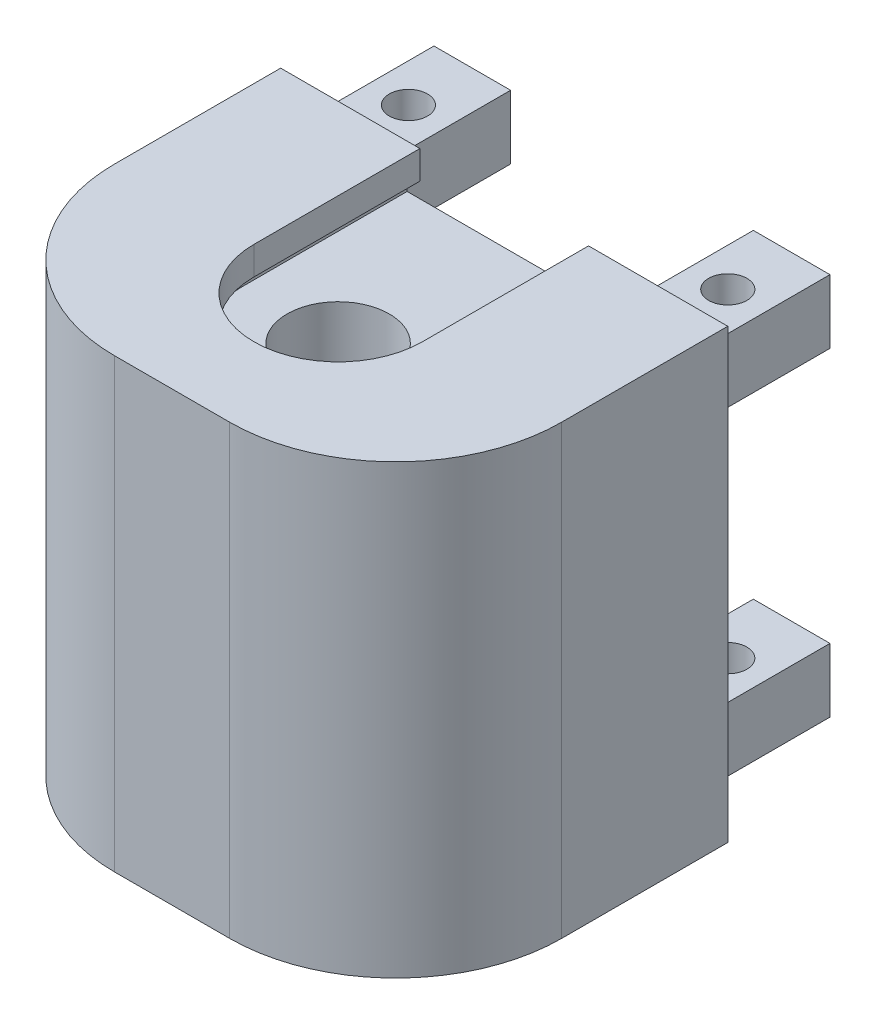
SolidWorks part; units mm, degrees
ref_plane "Front Plane" through (0, 0, 0) normal (0, 0, 1) x (1, 0, 0)
ref_plane "Top Plane" through (0, 0, 0) normal (0, 1, 0) x (1, 0, 0)
ref_plane "Right Plane" through (0, 0, 0) normal (1, 0, 0) x (0, 0, -1)
sketch "Sketch1" plane through (0, 0, 0) normal (0, 1, 0) x (1, 0, 0)
  line L0 (0, 0) -> (6, 0)
  line L1 (6, 0) -> (6, -10)
  line L2 (6, -10) -> (25, -10)
  line L3 (25, -10) -> (25, 0)
  line L4 (25, 0) -> (31, 0)
  line L5 (31, 0) -> (31, -10)
  line L7 (0, -10) -> (0, 0)
  line L8 (0, -10) -> (-2, -10)
  line L11 (33, -36) -> (33, -10)
  line L12 (33, -10) -> (31, -10)
  line L13 (3, 0) -> (3, -5) construction
  line L14 (15.5, -10) -> (15.5, 0) construction
  line L15 (33, -36) -> (-2, -36)
  line L16 (-2, -36) -> (-2, -10)
  circle A0 centre (3, -5) radius 1.5
  circle A1 centre (28, -5) radius 1.5
  dimension "D9" = 3
  dimension "D1" = 36
  dimension "D2" = 35
  dimension "D3" = 10
  dimension "D4" = 6
  dimension "D5" = 2
  dimension "D6" = 6
  dimension "D7" = 2
  dimension "D8" = 5
sketch "Sketch10" plane through (0, 0, 0) normal (0, 1, 0) x (1, 0, 0)
  line L0 (-2, -36) -> (33, -36)
  line L1 (33, -36) -> (33, -10)
  line L2 (33, -10) -> (-2, -10)
  line L3 (-2, -36) -> (-2, -10)
extrude "Boss-Extrude4" add sketch "Sketch10" along normal blind 2.5
extrude "Boss-Extrude5" add sketch "Sketch1" against normal blind 5
sketch "Sketch11" plane through (0, -5, 0) normal (0, -1, 0) x (1, 0, 0)
  line L0 (-2, 36) -> (-2, 10)
  line L1 (-2, 10) -> (33, 10)
  line L2 (33, 10) -> (33, 36)
  line L3 (33, 36) -> (-2, 36)
extrude "Boss-Extrude6" add sketch "Sketch11" along normal blind 2.5
ref_plane "Plane1" through (0, -2.5, 0) normal (0, 1, 0) x (1, 0, 0)
sketch "Sketch3" plane through (0, 0, 10) normal (0, 0, -1) x (-1, 0, 0)
  line L0 (-22.1, 2.5) -> (-22.1, 0.2875)
  line L2 (-22.1, 0.2875) -> (-23.1, 0.2875)
  line L3 (-23.1, 0.2875) -> (-23.1, -0.9125)
  line L4 (-23.1, -0.9125) -> (-15.5, -0.9125)
  line L5 (-15.5, -0.9125) -> (-7.9, -0.9125)
  line L6 (-7.9, -0.9125) -> (-7.9, 0.2875)
  line L7 (-7.9, 0.2875) -> (-8.9, 0.2875)
  line L8 (-8.9, 0.2875) -> (-8.9, 2.5)
  line L9 (-8.9, 2.5) -> (-22.1, 2.5)
  line L10 (-25, -2.5) -> (-6, -2.5) construction
  line L13 (-15.5, -2.5) -> (-15.5, -0.9125) construction
  line L14 (-33, 2.5) -> (2, 2.5) construction
  line L15 (-6, -5) -> (-6, 0) construction
  line L16 (-25, -5) -> (-25, 0) construction
  dimension "D1" = 1.2
  dimension "D2" = 3.4125
  dimension "D3" = 13.2
  dimension "D4" = 15.2
extrude "Cut-Extrude1" cut sketch "Sketch3" against normal blind 13 and the other way through all
sketch "Sketch4" plane through (0, -0.9125, 0) normal (0, 1, 0) x (1, 0, 0)
  line L1 (23.1, -23) -> (7.9, -23) construction
  circle A0 centre (15.5, -23) radius 7.6
  dimension "D1" = 15.2
extrude "Cut-Extrude2" cut sketch "Sketch4" along normal up to surface (1.2 mm away) up to face at (8.4, 0.2875, 16.5)
sketch "Sketch5" plane through (0, -0.9125, 0) normal (0, 1, 0) x (1, 0, 0)
  line L1 (8.9, -23) -> (22.1, -23) construction
  circle A0 centre (15.5, -23) radius 6.6
  dimension "D1" = 13.2
extrude "Cut-Extrude3" cut sketch "Sketch5" along normal through all
sketch "Sketch12" plane through (0, -7.5, 0) normal (0, -1, 0) x (1, 0, 0)
  line L4 (33, 36) -> (-2, 36)
  line L5 (-2, 36) -> (-2, 10)
  line L6 (-2, 10) -> (33, 10)
  line L7 (33, 10) -> (33, 36)
  line L8 (33, 36) -> (-2, 36)
  line L9 (-2, 36) -> (-2, 10)
  line L10 (-2, 10) -> (33, 10)
  line L11 (33, 10) -> (33, 36)
  dimension "D1" = 0
extrude "Boss-Extrude7" add sketch "Sketch12" along normal blind 15
sketch "Sketch13" plane through (0, -22.5, 0) normal (0, -1, 0) x (1, 0, 0)
  line L4 (33, 10) -> (33, 36)
  line L5 (33, 36) -> (-2, 36)
  line L6 (-2, 36) -> (-2, 10)
  line L7 (-2, 10) -> (33, 10)
  line L8 (33, 10) -> (33, 36)
  line L9 (33, 36) -> (-2, 36)
  line L10 (-2, 36) -> (-2, 10)
  line L11 (-2, 10) -> (33, 10)
  dimension "D1" = 0
extrude "Boss-Extrude8" add sketch "Sketch13" along normal blind 2.5
sketch "Sketch14" plane through (0, -25, 0) normal (0, -1, 0) x (1, 0, 0)
  line L12 (0, 0) -> (6, 0)
  line L13 (6, 0) -> (6, 10)
  line L14 (6, 10) -> (25, 10)
  line L15 (25, 10) -> (25, 0)
  line L16 (25, 0) -> (31, 0)
  line L17 (31, 0) -> (31, 10)
  line L18 (31, 10) -> (33, 10)
  line L19 (33, 10) -> (33, 36)
  line L20 (33, 36) -> (-2, 36)
  line L21 (-2, 36) -> (-2, 10)
  line L22 (-2, 10) -> (0, 10)
  line L23 (0, 10) -> (0, 0)
  line L24 (0, 0) -> (6, 0)
  line L25 (6, 0) -> (6, 10)
  line L26 (6, 10) -> (25, 10)
  line L27 (25, 10) -> (25, 0)
  line L28 (25, 0) -> (31, 0)
  line L29 (31, 0) -> (31, 10)
  line L30 (31, 10) -> (33, 10)
  line L31 (33, 10) -> (33, 36)
  line L32 (33, 36) -> (-2, 36)
  line L33 (-2, 36) -> (-2, 10)
  line L34 (-2, 10) -> (0, 10)
  line L35 (0, 10) -> (0, 0)
  circle A1 centre (3, 5) radius 1.5
  circle A2 centre (3, 5) radius 1.5
  circle A3 centre (28, 5) radius 1.5
  circle A4 centre (28, 5) radius 1.5
  dimension "D1" = 0
  dimension "D2" = 0
  dimension "D3" = 0
extrude "Boss-Extrude9" add sketch "Sketch14" along normal blind 5
sketch "Sketch15" plane through (0, -30, 0) normal (0, -1, 0) x (1, 0, 0)
  line L4 (33, 36) -> (-2, 36)
  line L5 (33, 10) -> (33, 36)
  line L6 (-2, 10) -> (33, 10)
  line L7 (-2, 36) -> (-2, 10)
  line L8 (33, 36) -> (-2, 36)
  line L9 (33, 10) -> (33, 36)
  line L10 (-2, 10) -> (33, 10)
  line L11 (-2, 36) -> (-2, 10)
  dimension "D1" = 0
extrude "Boss-Extrude10" add sketch "Sketch15" along normal blind 2.5
ref_plane "Plane4" through (0, -15, 0) normal (0, 1, 0) x (1, 0, 0)
mirror "Mirror8" about plane through (0, -15, 0) normal (0, 1, 0) of "Cut-Extrude3", "Cut-Extrude2", "Cut-Extrude1"
sketch "Sketch8" plane through (0, -0.9125, 0) normal (0, 1, 0) x (1, 0, 0)
  circle A0 centre (15.5, -23) radius 4
  dimension "D1" = 8
extrude "Cut-Extrude6" cut sketch "Sketch8" against normal through all
fillet "Fillet1" radius 13 2 edges at (-2, -15, 36) (33, -15, 36)
